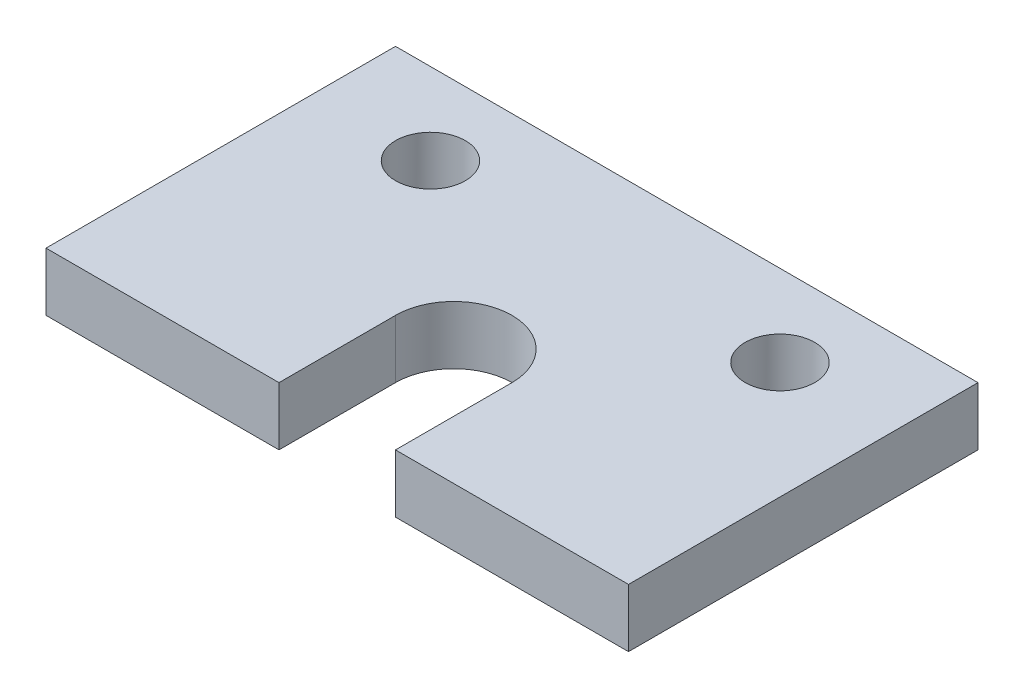
SolidWorks part; units mm, degrees
material "6061 Alloy"
ref_plane "Front Plane" through (0, 0, 0) normal (0, 0, 1) x (1, 0, 0)
ref_plane "Top Plane" through (0, 0, 0) normal (0, 1, 0) x (1, 0, 0)
ref_plane "Right Plane" through (0, 0, 0) normal (1, 0, 0) x (0, 0, -1)
sketch "Sketch1" plane through (0, 0, 0) normal (0, 1, 0) x (1, 0, 0)
  line L1 (-15.875, -9.525) -> (15.875, -9.525)
  line L2 (-15.875, -9.525) -> (-15.875, 9.525)
  line L3 (-15.875, 9.525) -> (15.875, 9.525)
  line L4 (15.875, -9.525) -> (15.875, 9.525)
  line L5 (-15.875, -9.525) -> (15.875, 9.525) construction
  line L6 (-15.875, 9.525) -> (15.875, -9.525) construction
  point P0 (0, 0)
  dimension "D1" = 19.05
  dimension "D2" = 31.75
extrude "Boss-Extrude1" add sketch "Sketch1" along normal blind 3.175
sketch "Sketch2" plane through (0, 3.175, 0) normal (0, 1, 0) x (1, 0, 0)
  line L0 (0, -55) -> (0, 55) construction
  line L1 (-55, 0) -> (55, 0) construction
  line L2 (-3.175, -3.175) -> (-3.175, -9.525)
  line L3 (-15.875, -9.525) -> (15.875, -9.525) construction
  line L4 (-3.175, -9.525) -> (3.175, -9.525)
  line L5 (3.175, -9.525) -> (3.175, -3.175)
  arc A0 (3.175, -3.175) -> (-3.175, -3.175) centre (0, -3.175) ccw
  dimension "D1" = 6.35
extrude "Cut-Extrude1" cut sketch "Sketch2" against normal through all
sketch "Sketch3" plane through (0, 3.175, 0) normal (0, 1, 0) x (1, 0, 0)
  line L0 (-9.525, 5.08) -> (9.525, 5.08) construction
  line L1 (0, -1.7463) -> (0, 1.7463) construction
  line L2 (-1.7463, 0) -> (1.7463, 0) construction
  point P0 (-9.525, 5.08)
  point P1 (9.525, 5.08)
  point P4 (0, 5.08)
  dimension "D1" = 19.05
  dimension "D2" = 5.08
hole_wizard "#6 Clearance Hole1" positions "Sketch4" profile "Sketch5" hole size "#6" standard "ANSI Inch" end condition up to next
sketch "Sketch4" plane through (0, 3.175, 0) normal (0, 1, 0) x (1, 0, 0)
  point P0 (-9.525, 5.08)
  point P3 (9.525, 5.08)
sketch "Sketch5" plane through (-9.525, 3.175, -5.08) normal (1, 0, 0) x (0, 0, 1)
  line L0 (0, 0) -> (0, 3.175)
  line L1 (0, 3.175) -> (1.8986, 3.175)
  line L2 (1.8986, 3.175) -> (1.8986, 0)
  line L5 (1.8986, 0) -> (0, 0)
  line L11 (0, -6.35) -> (0, 107.95) construction
  dimension "Thru Hole Dia." = 3.7973
  dimension "Thru Hole Depth" = 3.175
